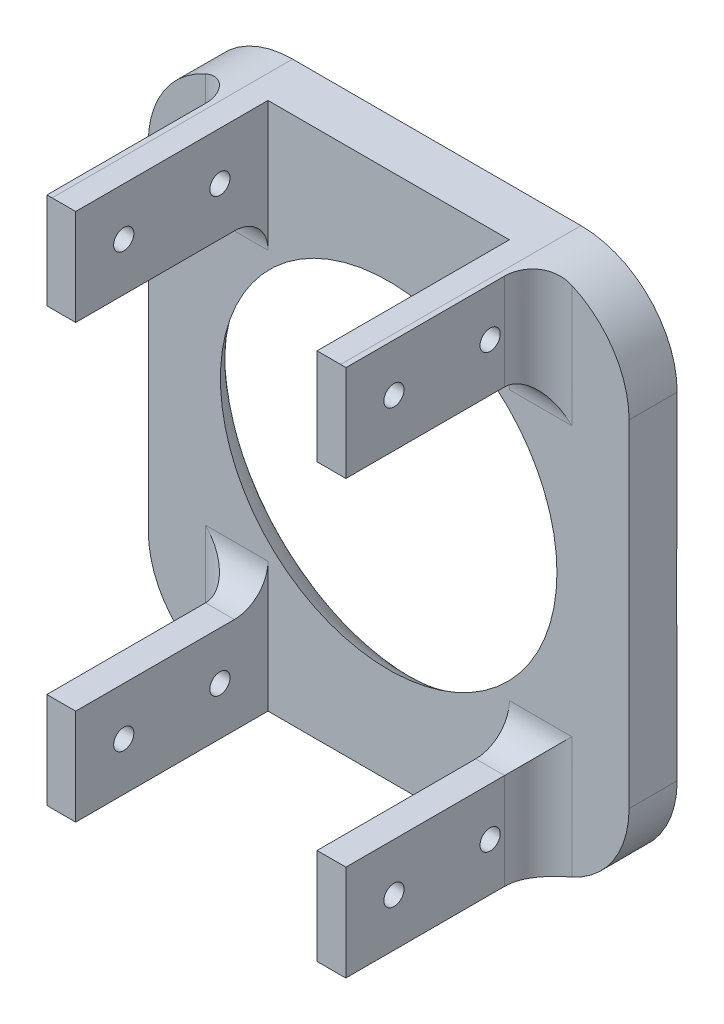
SolidWorks part; units mm, degrees
ref_plane "前视基准面" through (0, 0, 0) normal (0, 0, 1) x (1, 0, 0)
ref_plane "上视基准面" through (0, 0, 0) normal (0, 1, 0) x (1, 0, 0)
ref_plane "右视基准面" through (0, 0, 0) normal (1, 0, 0) x (0, 0, -1)
sketch "草图1" plane through (0, 0, 0) normal (0, 0, 1) x (1, 0, 0)
  line L1 (-50, 55) -> (50, 55)
  line L2 (-50, 55) -> (-50, -55)
  line L3 (-50, -55) -> (50, -55)
  line L4 (50, 55) -> (50, -55)
  line L5 (-50, 55) -> (50, -55) construction
  line L6 (-50, -55) -> (50, 55) construction
  circle A0 centre (0, 0) radius 35
  point P0 (0, 0)
  dimension "D3" = 70
  dimension "D1" = 100
  dimension "D2" = 110
extrude "凸台-拉伸1" add sketch "草图1" along normal blind 10
sketch "草图2" plane through (0, 0, 10) normal (0, 0, 1) x (1, 0, 0)
  line L0 (-25.1, 55) -> (-25.1, 35)
  line L1 (50, 55) -> (-50, 55) construction
  line L2 (-25.1, 35) -> (-31.1, 35)
  line L3 (-31.1, 35) -> (-31.1, 55)
  line L4 (-31.1, 55) -> (-25.1, 55)
  line L5 (0, 55) -> (0, 0) construction
  line L6 (31.1, 35) -> (31.1, 55)
  line L7 (25.1, 35) -> (31.1, 35)
  line L8 (25.1, 55) -> (25.1, 35)
  line L9 (31.1, 55) -> (25.1, 55)
  line L10 (0, 0) -> (-58.3405, 0) construction
  line L11 (25.1, -35) -> (31.1, -35)
  line L12 (25.1, -55) -> (25.1, -35)
  line L13 (31.1, -55) -> (25.1, -55)
  line L14 (31.1, -35) -> (31.1, -55)
  line L15 (-31.1, -35) -> (-31.1, -55)
  line L16 (-25.1, -35) -> (-31.1, -35)
  line L17 (-25.1, -55) -> (-25.1, -35)
  line L18 (-31.1, -55) -> (-25.1, -55)
  point P4 (0, 55)
  dimension "D1" = 20
  dimension "D2" = 6
  dimension "D3" = 25.1
extrude "凸台-拉伸2" add sketch "草图2" along normal blind 40
fillet "圆角1" radius 20 1 edges at (35, 0, 0)
fillet "圆角2" radius 7 8 edges at (31.1, -45, 10) (31.1, 45, 10) (-31.1, 45, 10) (-31.1, -45, 10) (-28.1, -35, 10) (28.1, -35, 10) (28.1, 35, 10) (-28.1, 35, 10)
sketch "草图3" plane through (-31.1, 0, 0) normal (-1, 0, 0) x (0, 0, 1)
  line L0 (10, 55) -> (10, -55) construction
  line L1 (50, -35) -> (17, -35) construction
  line L2 (0, 0) -> (85.1042, 0) construction
  circle A0 centre (20, -45) radius 2.1
  circle A1 centre (40, -45) radius 2.1
  circle A2 centre (40, 45) radius 2.1
  circle A3 centre (20, 45) radius 2.1
  dimension "D1" = 4.2
  dimension "D2" = 4.2
  dimension "D3" = 20
  dimension "D4" = 10
  dimension "D5" = 10
extrude "切除-拉伸1" cut sketch "草图3" against normal through all
fillet "圆角3" radius 20 4 edges at (50, -55, 5) (50, 55, 5) (-50, 55, 5) (-50, -55, 5)
